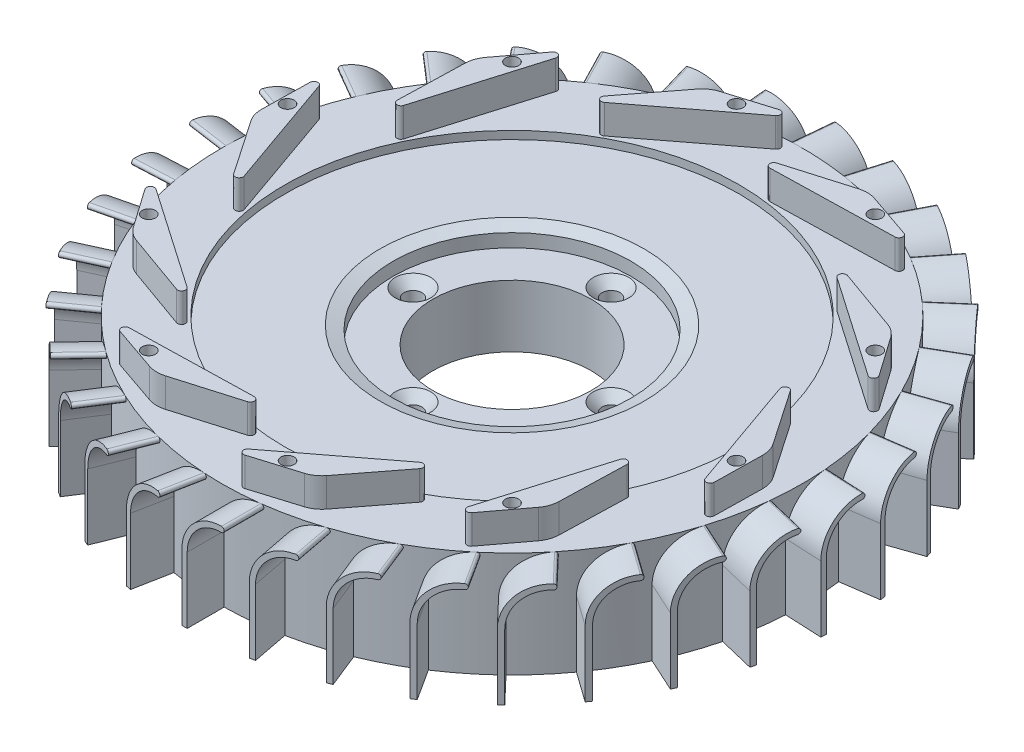
SolidWorks part; units mm, degrees
ref_plane "Ön Düzlem" through (0, 0, 0) normal (0, 0, 1) x (1, 0, 0)
ref_plane "Üst Düzlem" through (0, 0, 0) normal (0, 1, 0) x (1, 0, 0)
ref_plane "Sağ Düzlem" through (0, 0, 0) normal (1, 0, 0) x (0, 0, -1)
sketch "Çizim1" plane through (0, 0, 0) normal (0, 0, 1) x (1, 0, 0)
  line L0 (0, 0) -> (0, 33.5747) construction
  line L1 (-52, 11.9218) -> (-55, 11.9218)
  line L2 (-55, 11.9218) -> (-55, 31.9218)
  line L3 (-55, 31.9218) -> (-43, 31.9218)
  line L4 (-43, 31.9218) -> (-43, 30.4218)
  line L5 (-43, 30.4218) -> (-25, 30.4218)
  line L6 (-25, 30.4218) -> (-22.5, 29.6575)
  line L7 (-22.5, 29.6575) -> (-22.5, 27.1718)
  line L8 (-22.5, 27.1718) -> (-15, 27.1718)
  line L9 (-15, 27.1718) -> (-15, 15.4218)
  line L10 (-15, 15.4218) -> (-22.5, 15.4218)
  line L11 (-22.5, 15.4218) -> (-22.5, 10.4218)
  line L12 (-22.5, 10.4218) -> (-24.5, 10.4218)
  line L13 (-24.5, 10.4218) -> (-29.83, 21.9218)
  line L14 (-29.83, 21.9218) -> (-47, 21.9218)
  line L15 (-52, 16.9218) -> (-52, 11.9218)
  arc A0 (-47, 21.9218) -> (-52, 16.9218) centre (-47, 16.9218) ccw
  point P9 (-38.415, 21.9218)
  dimension "D16" = 5
  dimension "D1" = 55
  dimension "D2" = 15
  dimension "D3" = 7.5
  dimension "D4" = 7.5
  dimension "D5" = 2
  dimension "D6" = 25
  dimension "D7" = 43
  dimension "D8" = 107
  dimension "D9" = 3
  dimension "D10" = 1.5
  dimension "D11" = 10
  dimension "D12" = 20
  dimension "D13" = 5
  dimension "D14" = 11.75
  dimension "D15" = 16.5
  dimension "D17" = 17.17
revolve "Döndür1" add sketch "Çizim1" angle 360 about L0
ref_plane "Düzlem2" through (0, 0, 53) normal (0, 0, 1) x (1, 0, 0)
sketch "Çizim2" plane through (0, 0, 53) normal (0, 0, 1) x (1, 0, 0)
  line L0 (0, 0) -> (0, 11.9218) construction
  line L1 (0.5, 11.9218) -> (-0.5, 11.9218)
  line L2 (0.5, 11.9218) -> (0.5, 24.4218)
  line L3 (-0.5, 11.9218) -> (-0.5, 24.4218)
  line L4 (0.5, 24.4218) -> (7, 24.4218) construction
  line L5 (7, 24.4218) -> (7, 30.9218) construction
  line L7 (-55, 11.9218) -> (55, 11.9218) construction
  line L9 (0, 27.1144) -> (0, 44.7372) construction
  arc A1 (7, 31.9218) -> (-0.5, 24.4218) centre (7, 24.4218) ccw
  arc A2 (7, 30.9218) -> (0.5, 24.4218) centre (7, 24.4218) ccw
  arc A3 (7, 30.9218) -> (7, 31.9218) centre (7, 31.4218) ccw
extrude "Yükseklik-Ekstrüzyon1" add sketch "Çizim2" along normal blind 9
pattern_circular "Dairesel Kaplama1" count 33 over 360 about axis through (0, 0, 0) along (0, -1, 0) of "Yükseklik-Ekstrüzyon1" reverse direction yes
sketch "Çizim3" plane through (0, 31.9218, 0) normal (0, 1, 0) x (1, 0, 0)
  line L0 (0, 0) -> (0, 43) construction
  line L1 (5.4656, 44.6064) -> (17.5006, 48.1435)
  line L2 (20.5358, 48.0748) -> (29.0382, 45.1523)
  line L3 (28.8124, 43.6932) -> (5.6952, 43.137)
  arc A0 (29.0382, 45.1523) -> (28.8124, 43.6932) centre (28.7944, 44.443) cw
  arc A1 (5.6952, 43.137) -> (5.4656, 44.6064) centre (5.6771, 43.8868) cw
  arc A2 (17.5006, 48.1435) -> (20.5358, 48.0748) centre (18.9105, 43.3464) cw
  point P9 (32.9905, 43.7938)
  dimension "D4" = 0.75
  dimension "D5" = 5
  dimension "D1" = 43
  dimension "D2" = 33
  dimension "D3" = 15
extrude "Yükseklik-Ekstrüzyon2" add sketch "Çizim3" along normal blind 5.5
pattern_circular "Dairesel Kaplama2" count 10 over 360 about axis through (0, 0, 0) along (0, -1, 0) of "Yükseklik-Ekstrüzyon2" reverse direction yes
sketch "Çizim7" plane through (0, 37.4218, 0) normal (0, 1, 0) x (1, 0, 0)
  line L0 (0, 0) -> (0, 82.5732) construction
  point P3 (-8, 50.5)
  dimension "D1" = 50.5
  dimension "D2" = 8
hole_wizard "M3 Dişli Delik3" positions "3B Çizim4" profile "Çizim8" tap size "M3" standard "ISO"
sketch3d "3B Çizim4"
  point P0 (-8, 37.4218, -50.5)
cosmetic thread "Delik Dişi3" parameters "D1"=6, "D2"=3
sketch "Çizim8" plane through (-8, 37.4218, -50.5) normal (1, 0, 0) x (0, 0, 1)
  line L0 (0, 0) -> (0, 8.2511)
  line L1 (0, 8.2511) -> (1.25, 7.5)
  line L2 (1.25, 7.5) -> (1.25, 0)
  line L5 (1.25, 0) -> (0, 0)
  line L10 (0, 8.2511) -> (-1.25, 7.5) construction
  line L11 (0, -6.35) -> (0, 107.95) construction
  dimension "Tap Drill Dia." = 2.5
  dimension "Tap Drill Depth" = 7.5
  dimension "Drill Angle" = 118
pattern_circular "Dairesel Kaplama3" count 10 over 360 about axis through (0, 0, 0) along (0, -1, 0) of "M3 Dişli Delik3"
cosmetic thread "Delik Dişi4" parameters "D1"=6, "D2"=3
cosmetic thread "Delik Dişi5" parameters "D1"=6, "D2"=3
cosmetic thread "Delik Dişi6" parameters "D1"=6, "D2"=3
cosmetic thread "Delik Dişi7" parameters "D1"=6, "D2"=3
cosmetic thread "Delik Dişi8" parameters "D1"=6, "D2"=3
cosmetic thread "Delik Dişi9" parameters "D1"=6, "D2"=3
cosmetic thread "Delik Dişi10" parameters "D1"=6, "D2"=3
cosmetic thread "Delik Dişi11" parameters "D1"=6, "D2"=3
cosmetic thread "Delik Dişi12" parameters "D1"=6, "D2"=3
sketch "Çizim9" plane through (0, 27.1718, 0) normal (0, 1, 0) x (1, 0, 0)
  line L0 (0, 0) -> (0, 36.3017) construction
  point P3 (0, 18.75)
  dimension "D1" = 18.75
hole_wizard "M3 Altıgen Alyan Havşa Başlı Kör Vida İçin Havşa1" positions "3B Çizim5" profile "Çizim10" countersink size "M3" standard "ISO"
sketch3d "3B Çizim5"
  point P0 (0, 27.1718, -18.75)
sketch "Çizim10" plane through (0, 27.1718, -18.75) normal (1, 0, 0) x (0, 0, 1)
  line L0 (0, 0) -> (0, 12.7715)
  line L1 (0, 12.7715) -> (1.7, 11.75)
  line L2 (1.7, 11.75) -> (1.7, 1.66)
  line L3 (1.7, 1.66) -> (3.36, 0)
  line L5 (3.36, 0) -> (0, 0)
  line L6 (-1.7, 1.66) -> (-3.36, 0) construction
  line L10 (0, 12.7715) -> (-1.7, 11.75) construction
  line L11 (0, -6.35) -> (0, 107.95) construction
  dimension "Hole Dia." = 3.4
  dimension "Hole Depth" = 11.75
  dimension "Near C'Sink Dia." = 6.72
  dimension "Near C'Sink Angle" = 90
  dimension "Drill Angle" = 118
pattern_circular "Dairesel Kaplama4" count 4 over 360 about axis through (0, 0, 0) along (0, -1, 0) of "M3 Altıgen Alyan Havşa Başlı Kör Vida İçin Havşa1"
